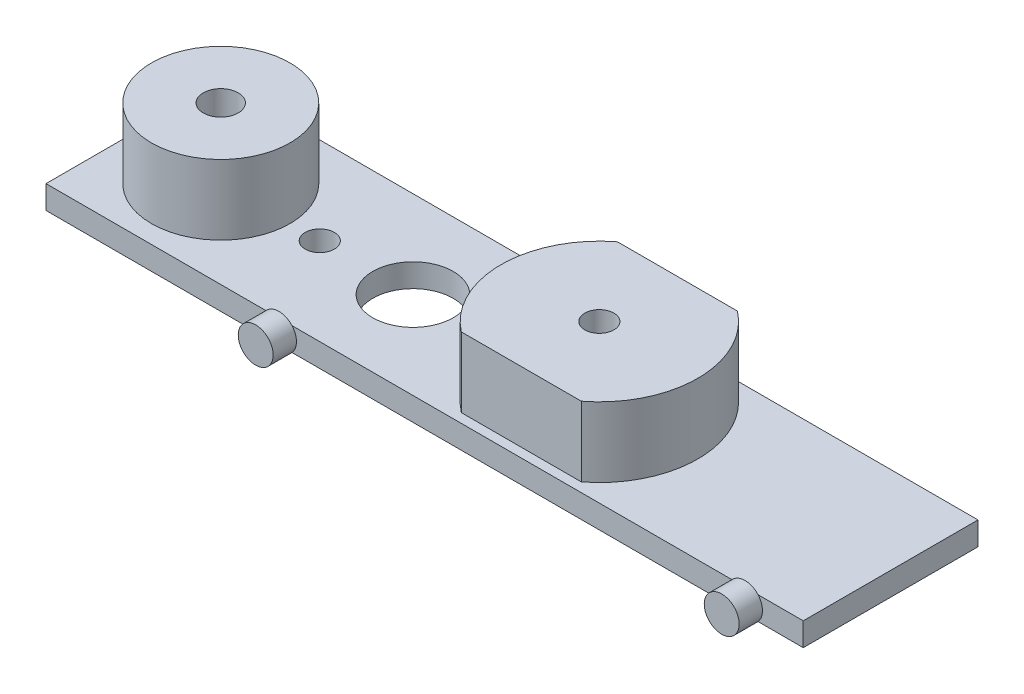
SolidWorks part; units mm, degrees
ref_plane "前视基准面" through (0, 0, 0) normal (0, 0, 1) x (1, 0, 0)
ref_plane "上视基准面" through (0, 0, 0) normal (0, 1, 0) x (1, 0, 0)
ref_plane "右视基准面" through (0, 0, 0) normal (1, 0, 0) x (0, 0, -1)
other "Configuration Table"
sketch "草图1" plane through (0, 0, 0) normal (0, 1, 0) x (1, 0, 0)
  line L0 (0, 7.5) -> (0, -7.5) construction
  line L1 (-25, 7.5) -> (25, 7.5)
  line L2 (-25, 7.5) -> (-25, -7.5)
  line L3 (-25, -7.5) -> (25, -7.5)
  line L4 (25, 7.5) -> (25, -7.5)
  line L5 (-25, 0) -> (25, 0) construction
  line L7 (-25, -7.5) -> (-40, -7.5)
  line L10 (-25, -7.5) -> (-25, 7.5)
  line L11 (-25, 7.5) -> (-40, 7.5)
  line L12 (-40, -7.5) -> (-40, 7.5)
  line L14 (-25, 7.5) -> (-40, 7.5)
  dimension "D1" = 50
  dimension "D2" = 15
  dimension "D6" = 15
  dimension "D7" = 15
extrude "凸台-拉伸1" add sketch "草图1" along normal blind 2 contours L11 L2 | L2 L1 L4 L3 | L10 L7 L12 L11 region at (-32.5, 0, 0)
sketch "草图2" plane through (0, 0, 0) normal (0, 1, 0) x (1, 0, 0)
  line L0 (0, 7.5) -> (0, -7.5) construction
  line L1 (25, 7.5) -> (-40, 7.5) construction
  line L2 (-32.5, 7.5) -> (-32.5, -7.5) construction
  line L3 (-40, -7.5) -> (-40, 7.5) construction
  line L4 (-25, 7.5) -> (-25, -7.5) construction
  line L5 (25, -7.5) -> (-40, -7.5) construction
  line L6 (-25, -7.5) -> (25, -7.5) construction
  line L10 (-40, 0) -> (-25, 0) construction
  line L14 (-40, -7.5) -> (25, -7.5) construction
  circle A2 centre (0, 0) radius 1.25
  circle A3 centre (16, 0) radius 4.1
  circle A4 centre (16, 0) radius 3.45
  circle A5 centre (-16, 0) radius 4.1
  circle A6 centre (-16, 0) radius 3.45
  circle A8 centre (24, 0) radius 1.25
  circle A9 centre (-24, 0) radius 1.25
  circle A11 centre (-32.5, 0) radius 1.5
  point P0 (-32.5, 0.301)
  point P36 (0, -7.5)
  dimension "D3" = 2.5
  dimension "D4" = 6.9
  dimension "D5" = 8.2
  dimension "D7" = 15
  dimension "D8" = 2.5
  dimension "D11" = 3
  dimension "D2" = 7.5
  dimension "D6" = 16
  dimension "D10" = 8
  dimension "D17" = 7.5
extrude "切除-拉伸1" cut sketch "草图2" along normal up to surface (2 mm away) contours A2 | A9 | A6 | A11 up to face at (-7.5, 2, 0)
sketch "草图4" plane through (0, 0, 7.5) normal (0, 0, 1) x (1, 0, 0)
  line L0 (25, 1) -> (-40, 1) construction
  line L1 (25, 2) -> (25, 0) construction
  line L2 (-40, 2) -> (-40, 0) construction
  line L3 (0, 0) -> (0, 2) construction
  line L5 (25, 2) -> (25, 0) construction
  line L6 (-40, 2) -> (25, 2) construction
  circle A0 centre (20, 1) radius 1.5
  circle A1 centre (-20, 1) radius 1.5
  dimension "D1" = 3
  dimension "D2" = 3
  dimension "D3" = 20
  dimension "D4" = 20
  dimension "D5" = 25
extrude "凸台-拉伸2" add sketch "草图4" along normal blind 2
sketch "草图5" plane through (0, 2, 0) normal (0, 1, 0) x (1, 0, 0)
  line L0 (0, 0) -> (0, 4.126) construction
  line L1 (4.9054, -6) -> (-4.9054, -6)
  line L2 (-4.7026, 0) -> (-2.9861, 0) construction
  line L3 (4.9054, 6) -> (-4.9054, 6)
  line L4 (5.149, -6.7) -> (-5.149, -6.7)
  line L5 (5.149, 6.7) -> (-5.149, 6.7)
  arc A0 (-4.9054, 6) -> (-4.9054, -6) centre (0, 0) ccw
  arc A1 (4.9054, -6) -> (4.9054, 6) centre (0, 0) ccw
  arc A2 (-5.149, 6.7) -> (-5.149, -6.7) centre (0, 0) ccw
  arc A3 (5.149, -6.7) -> (5.149, 6.7) centre (0, 0) ccw
  circle A4 centre (-32.5, 0) radius 5.95
  circle A5 centre (-32.5, 0) radius 5.25
  point P14 (0, -6)
  point P15 (0, 6)
  point P21 (0, -6.7)
  point P22 (0, 6.7)
  circle M9 centre (0, 0) radius 1.25
  dimension "D1" = 15.5
  dimension "D3" = 16.9
  dimension "D5" = 10.5
  dimension "D6" = 11.9
  dimension "D2" = 12
  dimension "D4" = 13.4
extrude "凸台-拉伸3" add sketch "草图5" along normal blind 6
extrude "凸台-拉伸4" add sketch "草图5<8>" along direction (0, 1, 0) on the side of the normal up to surface (6 mm away) contours L1 A1 L3 A0 M9 | A5 region at (0, 2, 5.804) up to face at (0, 8, 0)
sketch "草图5<8>" plane through (0, 2, 0) normal (0, 1, 0) x (1, 0, 0) same geometry as "草图5"
extrude "切除-拉伸2" cut sketch "草图5<11>" against normal through all and the other way offset from surface 2.5 contours L1 A1 L3 A0 M9 | A5 region at (0, 2, 5.804) other way up to face at (0, 8, 0)
sketch "草图5<11>" plane through (0, 2, 0) normal (0, 1, 0) x (1, 0, 0) same geometry as "草图5"
extrude "切除-拉伸3" cut sketch "草图2<3>" along normal up to surface (8 mm away) contours A11 up to face at (-32.5, 8, 5.95)
sketch "草图2<3>" plane through (0, 0, 0) normal (0, 1, 0) x (1, 0, 0) same geometry as "草图2"
